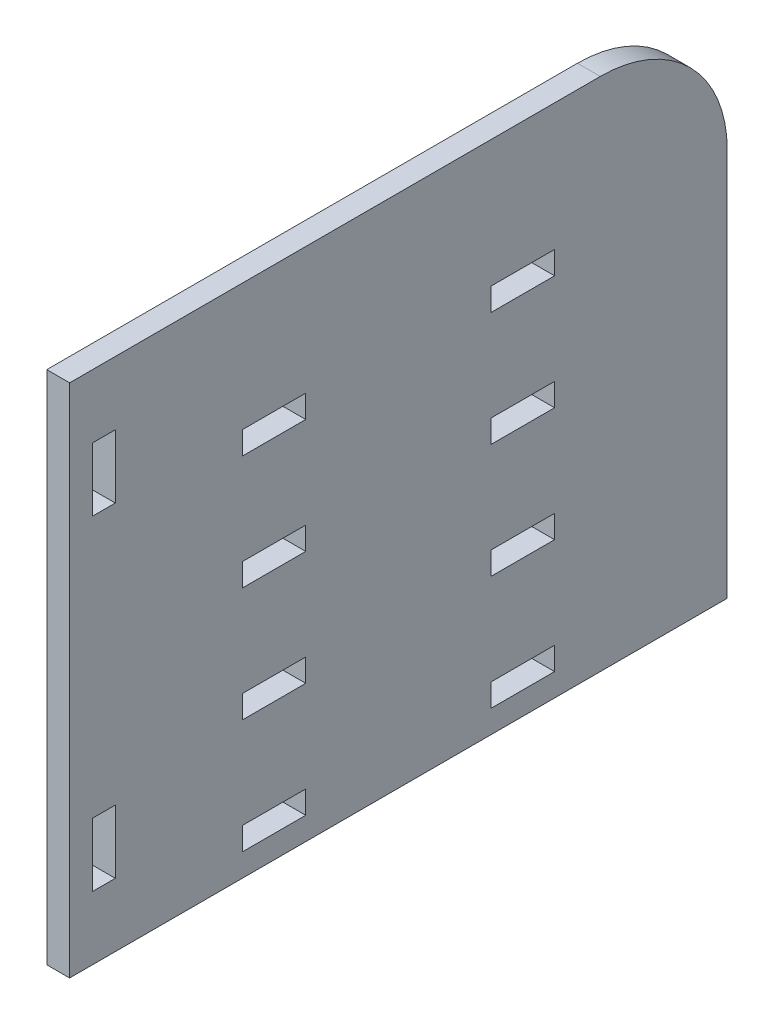
SolidWorks part; units mm, degrees
material "Maple"
ref_plane "Front Plane" through (0, 0, 0) normal (0, 0, 1) x (1, 0, 0)
ref_plane "Top Plane" through (0, 0, 0) normal (0, 1, 0) x (1, 0, 0)
ref_plane "Right Plane" through (0, 0, 0) normal (1, 0, 0) x (0, 0, -1)
sketch "Sketch1" plane through (0, 0, 0) normal (1, 0, 0) x (0, 0, -1)
  line L0 (-155.8318, -145.8488) -> (-414.8318, -145.8488) construction
  line L1 (-414.8318, 57.1512) -> (3.1682, 57.1512)
  line L2 (-414.8318, 57.1512) -> (-414.8318, -348.8488)
  line L3 (-414.8318, -348.8488) -> (103.1682, -348.8488)
  line L4 (103.1682, -42.8488) -> (103.1682, -348.8488)
  line L5 (-414.8318, 57.1512) -> (103.1682, -348.8488) construction
  line L6 (-414.8318, -348.8488) -> (103.1682, 57.1512) construction
  line L7 (-396.8318, 7.1512) -> (-378.8318, 7.1512)
  line L8 (-396.8318, 7.1512) -> (-396.8318, -42.8488)
  line L9 (-396.8318, -42.8488) -> (-378.8318, -42.8488)
  line L10 (-378.8318, 7.1512) -> (-378.8318, -42.8488)
  line L11 (-396.8318, -248.8488) -> (-378.8318, -248.8488)
  line L12 (-378.8318, -298.8488) -> (-378.8318, -248.8488)
  line L13 (-396.8318, -298.8488) -> (-378.8318, -298.8488)
  line L14 (-396.8318, -298.8488) -> (-396.8318, -248.8488)
  line L15 (-155.8318, -145.8488) -> (-155.8318, -348.8488) construction
  line L16 (-278.8318, -312.8488) -> (-228.8318, -312.8488)
  line L17 (-278.8318, -312.8488) -> (-278.8318, -330.8488)
  line L18 (-278.8318, -330.8488) -> (-228.8318, -330.8488)
  line L19 (-228.8318, -312.8488) -> (-228.8318, -330.8488)
  line L20 (-278.8318, -312.8488) -> (-228.8318, -330.8488) construction
  line L21 (-278.8318, -330.8488) -> (-228.8318, -312.8488) construction
  line L22 (-32.8318, -330.8488) -> (-82.8318, -330.8488)
  line L23 (-82.8318, -312.8488) -> (-82.8318, -330.8488)
  line L24 (-32.8318, -312.8488) -> (-82.8318, -312.8488)
  line L25 (-32.8318, -312.8488) -> (-32.8318, -330.8488)
  line L26 (-278.8318, -222.8488) -> (-278.8318, -240.8488)
  line L27 (-278.8318, -222.8488) -> (-228.8318, -222.8488)
  line L28 (-228.8318, -222.8488) -> (-228.8318, -240.8488)
  line L29 (-278.8318, -240.8488) -> (-228.8318, -240.8488)
  line L30 (-32.8318, -240.8488) -> (-82.8318, -240.8488)
  line L31 (-82.8318, -222.8488) -> (-82.8318, -240.8488)
  line L32 (-32.8318, -222.8488) -> (-82.8318, -222.8488)
  line L33 (-32.8318, -222.8488) -> (-32.8318, -240.8488)
  line L34 (-278.8318, -132.8488) -> (-278.8318, -150.8488)
  line L35 (-278.8318, -132.8488) -> (-228.8318, -132.8488)
  line L36 (-228.8318, -132.8488) -> (-228.8318, -150.8488)
  line L37 (-278.8318, -150.8488) -> (-228.8318, -150.8488)
  line L38 (-32.8318, -150.8488) -> (-82.8318, -150.8488)
  line L39 (-82.8318, -132.8488) -> (-82.8318, -150.8488)
  line L40 (-32.8318, -132.8488) -> (-82.8318, -132.8488)
  line L41 (-32.8318, -132.8488) -> (-32.8318, -150.8488)
  line L42 (-278.8318, -42.8488) -> (-278.8318, -60.8488)
  line L43 (-278.8318, -42.8488) -> (-228.8318, -42.8488)
  line L44 (-228.8318, -42.8488) -> (-228.8318, -60.8488)
  line L45 (-278.8318, -60.8488) -> (-228.8318, -60.8488)
  line L46 (-32.8318, -60.8488) -> (-82.8318, -60.8488)
  line L47 (-82.8318, -42.8488) -> (-82.8318, -60.8488)
  line L48 (-32.8318, -42.8488) -> (-82.8318, -42.8488)
  line L49 (-32.8318, -42.8488) -> (-32.8318, -60.8488)
  arc A0 (103.1682, -42.8488) -> (3.1682, 57.1512) centre (3.1682, -42.8488) ccw
  point P0 (-155.8318, -145.8488)
  point P18 (-253.8318, -321.8488)
  dimension "D3" = 100
  dimension "D1" = 406
  dimension "D2" = 518
  dimension "D4" = 50
  dimension "D5" = 18
  dimension "D6" = 18
  dimension "D7" = 50
  dimension "D8" = 18
  dimension "D9" = 136
  dimension "D10" = 50
  dimension "D11" = 18
  dimension "D13" = 136
  dimension "D14" = 136
  dimension "D15" = 18
  dimension "D16" = 72
  dimension "D17" = 50
  dimension "D12" = 4
extrude "Boss-Extrude1" add sketch "Sketch1" along normal blind 18
